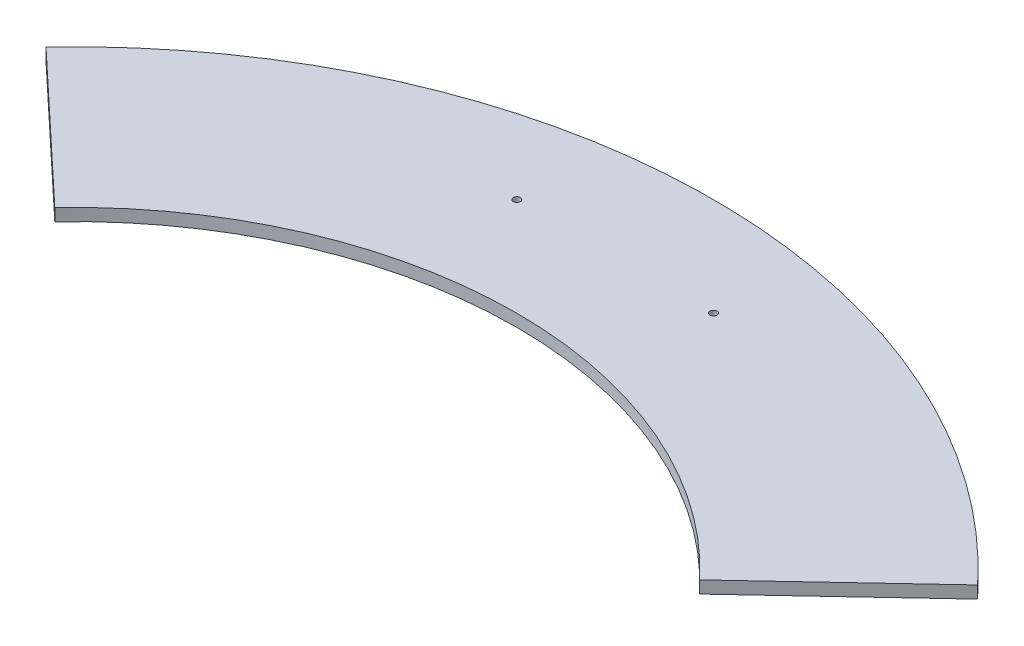
SolidWorks part; units mm, degrees
ref_plane "Front Plane" through (0, 0, 0) normal (0, 0, 1) x (1, 0, 0)
ref_plane "Top Plane" through (0, 0, 0) normal (0, 1, 0) x (1, 0, 0)
ref_plane "Right Plane" through (0, 0, 0) normal (1, 0, 0) x (0, 0, -1)
sketch "Sketch1" plane through (0, 0, 0) normal (0, 1, 0) x (1, 0, 0)
  line L0 (0, 202.946) -> (0, 253.746) construction
  line L1 (0, 0) -> (0, 202.946) construction
  line L2 (166.4945, 130.8737) -> (240.5743, 200.406)
  line L3 (0, 202.946) -> (0, 304.546) construction
  line L4 (-50.8, 253.746) -> (50.8, 253.746) construction
  line L5 (-166.4945, 130.8737) -> (-240.5743, 200.406)
  arc A0 (-240.5743, 200.406) -> (240.5743, 200.406) centre (0, -25.4) cw
  arc A1 (-166.4945, 130.8737) -> (166.4945, 130.8737) centre (0, -25.4) cw
  dimension "D2" = 329.946
  dimension "D5" = 228.346
  dimension "D1" = 50.8
  dimension "D3" = 101.6
  dimension "D4" = 25.4
  dimension "D6" = 50.8
  dimension "D7" = 53.34
  dimension "D8" = 122.8723
extrude "Boss-Extrude1" add sketch "Sketch1" along normal blind 6.35
ref_axis "Axis1" through (0, 6.35, -202.946) along (0, 0, -1)
hole_wizard "#6 Clearance Hole1" positions "3DSketch2" profile "Sketch3" hole size "#6" standard "Ansi Inch"
sketch3d "3DSketch2"
  line L0 (0, 6.35, -202.946) -> (0, 6.35, -304.546) construction
  line L1 (0, 6.35, -304.546) -> (0, 6.35, -248.3599) construction
  arc A1 (240.5743, 6.35, -200.406) -> (-240.5743, 6.35, -200.406) centre (0, 6.35, 25.4) ccw construction
  point P0 (-50.8, 6.35, -253.7463)
  point P2 (50.8, 6.35, -253.7463)
  point P16 (0, 336.296, 25.4)
  dimension "D1" = 50.8
  dimension "D2" = 50.8
  dimension "D3" = 101.6
  dimension "D4" = 71.8419
sketch "Sketch3" plane through (-50.8, 6.35, -253.7463) normal (1, 0, 0) x (0, 0, 1)
  line L0 (0, 0) -> (0, 26.4989)
  line L1 (0, 26.4989) -> (1.8288, 25.4)
  line L2 (1.8288, 25.4) -> (1.8288, 0)
  line L5 (1.8288, 0) -> (0, 0)
  line L10 (0, 26.4989) -> (-1.8288, 25.4) construction
  line L11 (0, -6.35) -> (0, 107.95) construction
  dimension "Hole Dia." = 3.6576
  dimension "Hole Depth" = 25.4
  dimension "Drill Angle" = 118
